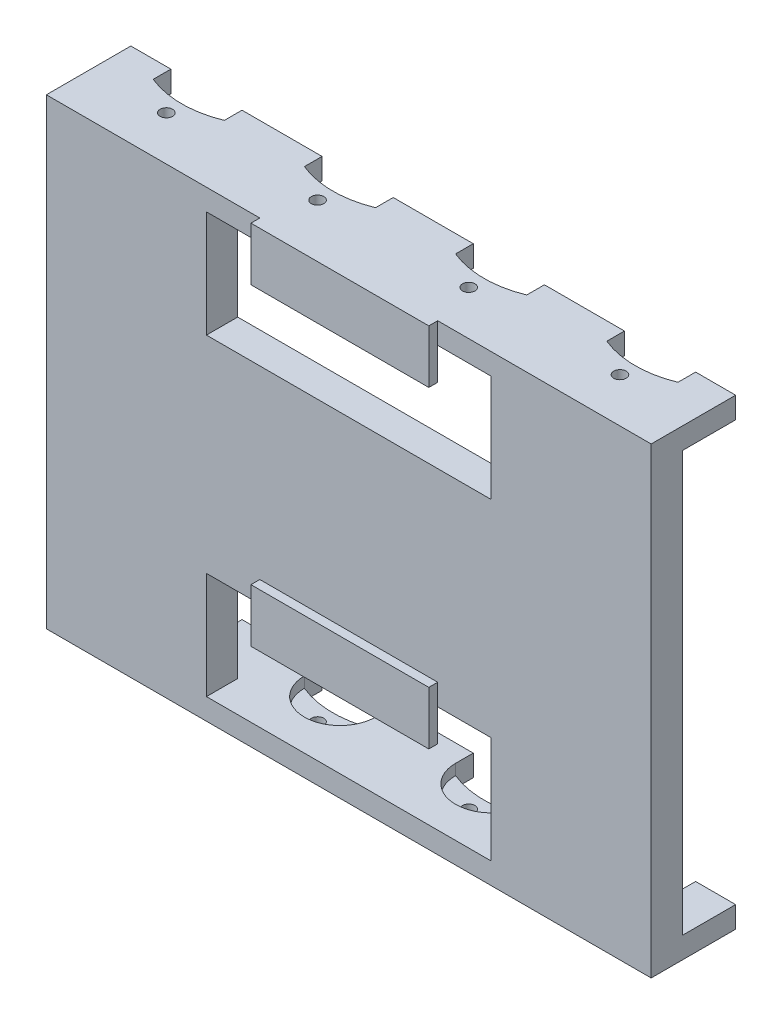
SolidWorks part; units mm, degrees
ref_plane "Front Plane" through (0, 0, 0) normal (0, 0, 1) x (1, 0, 0)
ref_plane "Top Plane" through (0, 0, 0) normal (0, 1, 0) x (1, 0, 0)
ref_plane "Right Plane" through (0, 0, 0) normal (1, 0, 0) x (0, 0, -1)
sketch "Sketch1" plane through (0, 0, 0) normal (0, 1, 0) x (1, 0, 0)
  line L0 (0, 0) -> (21.25, 0)
  line L1 (21.25, 0) -> (21.25, 23.7465)
  line L2 (21.25, 23.7465) -> (-21.25, 23.7465)
  line L3 (-21.25, 23.7465) -> (-21.25, 0)
  line L4 (-21.25, 0) -> (0, 0)
  line L5 (0, 0) -> (0, 23.7465) construction
  line L6 (-10, 18.7788) -> (-10, 23.7465)
  line L7 (10, 18.7788) -> (10, 23.7465)
  arc A0 (-10, 18.7788) -> (10, 18.7788) centre (0, 18.7788) ccw
  arc A1 (10, 18.7788) -> (-10, 18.7788) centre (0, 43.1409) cw
  circle A4 centre (0, 12.4788) radius 1.75
  point P11 (0, 8.7788)
  dimension "D2" = 10
  dimension "D4" = 3.5
  dimension "D1" = 42.5
  dimension "D3" = 3.7
extrude "Boss-Extrude1" add sketch "Sketch1" along normal blind 3 contours L4 L5 A0 L6 L2 L3 | L5 L0 L1 L2 L7 A0 | L5 A0 A1 A4 | A0 L5 A4 A1 region at (12.6988, 0, -10.0787) region at (-12.6988, 0, -10.0787) region at (-4.6267, 0, -13.9417) region at (4.6267, 0, -13.9417)
extrude "Boss-Extrude2" add sketch "Sketch1<3>" against normal blind 3 contours L4 L5 A0 L6 L2 L3 | L5 L0 L1 L2 L7 A0 region at (12.6988, 0, -10.0787) region at (-12.6988, 0, -10.0787)
sketch "Sketch1<3>" plane through (0, 0, 0) normal (0, 1, 0) x (1, 0, 0) same geometry as "Sketch1"
pattern_linear "LPattern1" count 4 spacing 42.5 along (1, 0, 0) of "Boss-Extrude2", "Boss-Extrude1"
sketch "Sketch2" plane through (0, -3, 0) normal (0, -1, 0) x (-1, 0, 0)
  line L0 (-148.75, 0) -> (-148.75, 23.7465) construction
  line L1 (-148.75, 8.7788) -> (21.25, 8.7788)
  line L2 (-148.75, 8.7788) -> (-148.75, 0)
  line L3 (-148.75, 0) -> (21.25, 0)
  line L4 (21.25, 8.7788) -> (21.25, 0)
  line L5 (21.25, 0) -> (-148.75, 0) construction
  arc A0 (-137.5, 18.7788) -> (-117.5, 18.7788) centre (-127.5, 18.7788) ccw construction
extrude "Boss-Extrude3" add sketch "Sketch2" along normal up to surface (118 mm away)
ref_plane "Plane1" through (0, -62, 0) normal (0, -1, 0) x (-1, 0, 0)
mirror "Mirror2" about plane through (0, -62, 0) normal (0, -1, 0) of bodies 104
ref_plane "Plane2" through (63.75, 0, 0) normal (-1, 0, 0) x (0, 0, 1)
sketch "Sketch4" plane through (63.75, 0, 0) normal (-1, 0, 0) x (0, 0, 1)
  line L0 (0, 3) -> (2.5, 3)
  line L1 (2.5, 3) -> (2.5, -12)
  line L2 (2.5, -12) -> (0, -12)
  line L3 (0, 3) -> (0, -127) construction
  line L4 (0, -12) -> (0, 3)
  line L5 (-8.7788, -3) -> (0, -3)
  line L6 (-8.7788, -33) -> (0, -33)
  line L7 (-8.7788, -121) -> (-8.7788, -3) construction
  line L8 (0, -33) -> (0, -12)
  line L9 (-8.7788, -3) -> (-8.7788, -33)
  line L10 (-8.7788, -121) -> (0, -121)
  line L11 (0, -121) -> (0, -91)
  line L12 (0, -91) -> (-8.7788, -91)
  line L13 (-8.7788, -91) -> (-8.7788, -121)
  line L14 (0, -85) -> (2.5, -85)
  line L15 (2.5, -85) -> (2.5, -100)
  line L16 (2.5, -100) -> (0, -100)
  line L18 (0, -85) -> (0, -91)
  dimension "D1" = 2.5
  dimension "D2" = 15
  dimension "D3" = 30
  dimension "D4" = 6
  dimension "D5" = 6
extrude "Boss-Extrude4" add sketch "Sketch4" along normal mid plane 50 contours L4 L2 L1 L0 | L14 L18 L11 L16 L15 region at (63.75, -4.5, 1.25) region at (63.75, -92.5, 1.25)
extrude "Cut-Extrude1" cut sketch "Sketch4<3>" against normal mid plane 80 contours L5 L9 L6 L8 L4 | L12 L13 L10 L11 region at (63.75, -18, -4.3894) region at (63.75, -106, -4.3894)
sketch "Sketch4<3>" plane through (63.75, 0, 0) normal (-1, 0, 0) x (0, 0, 1) same geometry as "Sketch4"
equation "\"D5@Sketch4\"=\"D4@Sketch4\""
